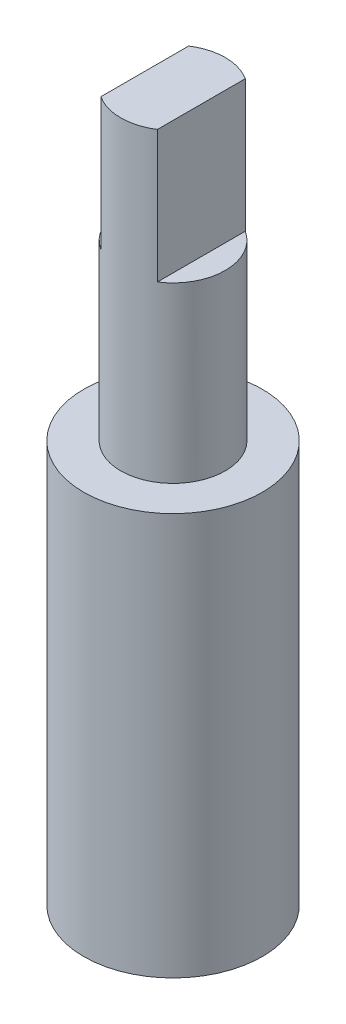
SolidWorks part; units mm, degrees
ref_plane "Front Plane" through (0, 0, 0) normal (0, 0, 1) x (1, 0, 0)
ref_plane "Top Plane" through (0, 0, 0) normal (0, 1, 0) x (1, 0, 0)
ref_plane "Right Plane" through (0, 0, 0) normal (1, 0, 0) x (0, 0, -1)
sketch "Sketch1" plane through (0, 0, 0) normal (0, 1, 0) x (1, 0, 0)
  circle A0 centre (0, 0) radius 3.075
  dimension "D1" = 6.15
extrude "Boss-Extrude1" add sketch "Sketch1" along normal blind 13.85
sketch "Sketch2" plane through (0, 13.85, 0) normal (0, 1, 0) x (1, 0, 0)
  circle A0 centre (0, 0) radius 1.8
  dimension "D1" = 3.6
extrude "Boss-Extrude2" add sketch "Sketch2" along normal blind 5.98
sketch "Sketch3" plane through (0, 19.83, 0) normal (0, 1, 0) x (1, 0, 0)
  line L0 (-0.975, 1.5131) -> (-0.975, -1.5131)
  line L1 (0.975, 1.5131) -> (0.975, -1.5131)
  circle A0 centre (0, 0) radius 1.8 construction
  circle A1 centre (0, 0) radius 1.8 construction
  arc A2 (-0.975, -1.5131) -> (0.975, -1.5131) centre (0, 0) ccw
  arc A3 (0.975, 1.5131) -> (-0.975, 1.5131) centre (0, 0) ccw
  point P4 (-1.8, 0)
  point P5 (1.8, 0)
  dimension "D1" = 1.95
  dimension "D2" = 0.975
extrude "Boss-Extrude3" add sketch "Sketch3" along normal blind 4.55
sketch "Sketch4" plane through (0, 0, 0) normal (0, -1, 0) x (1, 0, 0)
  circle A0 centre (0, 0) radius 2.15
  dimension "D1" = 4.3
extrude "Cut-Extrude1" cut sketch "Sketch4" against normal blind 1.95
